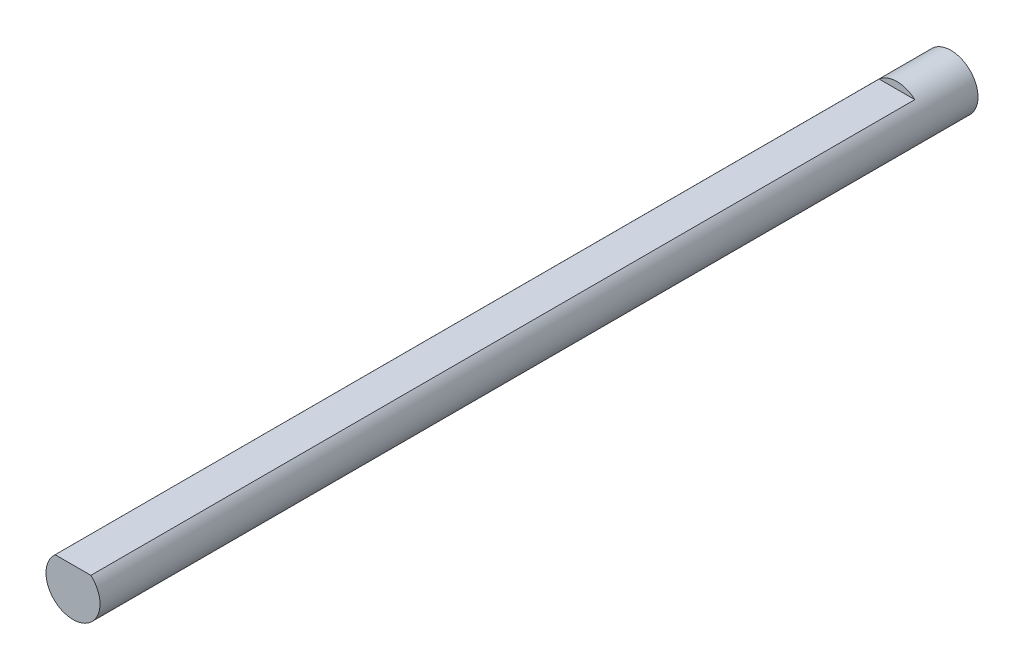
SolidWorks part; units mm, degrees
material "Stainless Steel (ferritic)"
ref_plane "Front Plane" through (0, 0, 0) normal (0, 0, 1) x (1, 0, 0)
ref_plane "Top Plane" through (0, 0, 0) normal (0, 1, 0) x (1, 0, 0)
ref_plane "Right Plane" through (0, 0, 0) normal (1, 0, 0) x (0, 0, -1)
sketch "Sketch1" plane through (0, 0, 0) normal (0, 0, 1) x (1, 0, 0)
  circle A0 centre (0, 0) radius 4
extrude "Boss-Extrude1" add sketch "Sketch1" along normal blind 65 and the other way blind 65
sketch "Sketch2" plane through (0, 0, 65) normal (0, 0, 1) x (1, 0, 0)
  line L0 (-2.6458, 3) -> (2.6458, 3)
  circle A1 centre (0, 0) radius 4 construction
  arc A2 (-2.6458, 3) -> (2.6458, 3) centre (0, 0) cw
  dimension "D1" = 3
extrude "Cut-Extrude1" cut sketch "Sketch2" against normal blind 122
